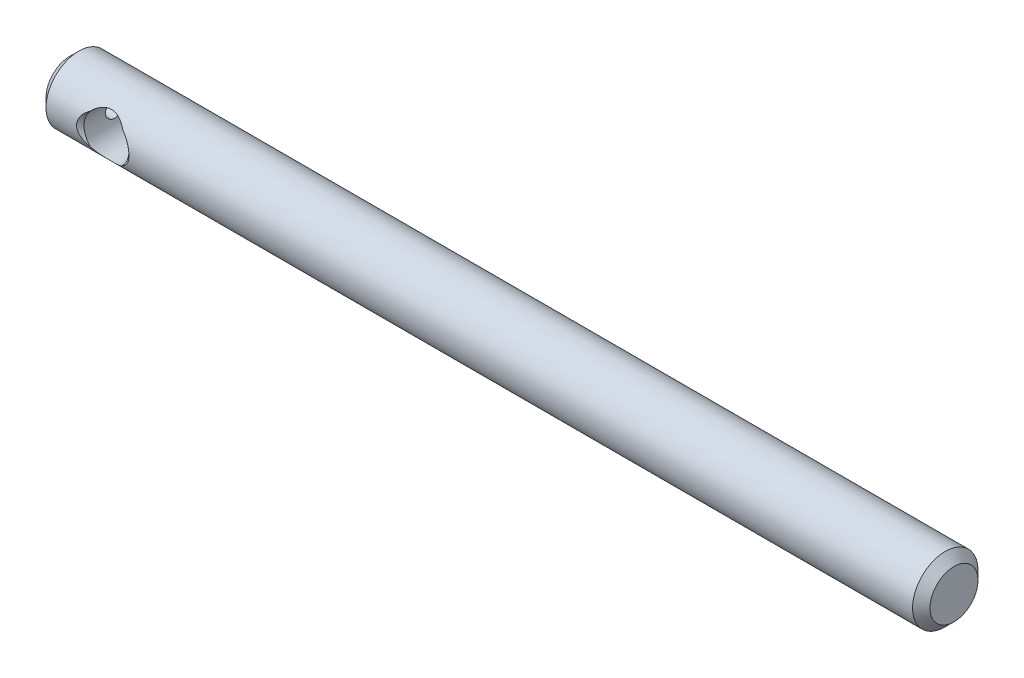
SolidWorks part; units mm, degrees
ref_plane "Front Plane" through (0, 0, 0) normal (0, 0, 1) x (1, 0, 0)
ref_plane "Top Plane" through (0, 0, 0) normal (0, 1, 0) x (1, 0, 0)
ref_plane "Right Plane" through (0, 0, 0) normal (1, 0, 0) x (0, 0, -1)
sketch "Sketch2" plane through (0, 0, 0) normal (1, 0, 0) x (0, 0, -1)
  circle A0 centre (0, 0) radius 4.7625
  dimension "D1" = 9.525
extrude "Boss-Extrude1" add sketch "Sketch2" along normal blind 128.651
chamfer "Chamfer1" distance 1.27 angle 45 2 edges at (0, 0, -4.7625) (128.651, 0, -4.7625)
ref_plane "Plane1" through (0, 0, 4.7625) normal (0, 0, 1) x (1, 0, 0)
sketch "Sketch7" plane through (0, 0, 4.7625) normal (0, 0, 1) x (1, 0, 0)
  line L0 (0, 3.4925) -> (0, -3.4925) construction
  line L1 (127.381, 4.7625) -> (1.27, 4.7625) construction
  point P0 (9.525, 0)
  point P5 (0, 0)
  dimension "D1" = 9.525
  dimension "D2" = 4.7625
hole_wizard "F (0.257) Diameter Hole2" positions "Sketch7" profile "Sketch9" hole size "F" standard "ANSI Inch" end condition through all
sketch "Sketch9" plane through (9.525, 0, 4.7625) normal (1, 0, 0) x (0, -1, 0)
  line L0 (0, 0) -> (0, 9.525)
  line L1 (0, 9.525) -> (3.81, 9.525)
  line L2 (3.2639, 8.9789) -> (3.2639, 0.5461)
  line L3 (3.2639, 0.5461) -> (3.81, 0)
  line L5 (3.81, 0) -> (0, 0)
  line L6 (-3.2639, 0.5461) -> (-3.81, 0) construction
  line L7 (3.81, 9.525) -> (3.2639, 8.9789)
  line L8 (-3.81, 9.525) -> (-3.2639, 8.9789) construction
  line L11 (0, -6.35) -> (0, 107.95) construction
  dimension "Thru Hole Dia." = 6.5278
  dimension "Thru Hole Depth" = 9.525
  dimension "Near C'Sink Dia." = 7.62
  dimension "Near C'Sink Angle" = 90
  dimension "Far C'Sink Dia." = 7.62
  dimension "Far C'Sink Angle" = 90
sketch "Sketch10" plane through (0, 0, 0) normal (-1, 0, 0) x (0, 0, 1)
  point P0 (0, 0)
  point P1 (0, 0)
hole_wizard "#4-40 Tapped Hole1" positions "Sketch10" profile "Sketch11" tap size "#4-40" standard "ANSI Inch" end condition up to next
cosmetic thread "Hole Thread1" parameters "D2"=2.8448
sketch "Sketch11" plane through (0, 0, 0) normal (0, 1, 0) x (0, 0, 1)
  line L0 (0, 0) -> (0, 6.2611)
  line L1 (0, 6.2611) -> (1.1303, 6.2611)
  line L2 (1.1303, 6.2611) -> (1.1303, 0.4572)
  line L3 (1.1303, 0.4572) -> (1.5875, 0)
  line L5 (1.5875, 0) -> (0, 0)
  line L6 (-1.1303, 0.4572) -> (-1.5875, 0) construction
  line L11 (0, -6.35) -> (0, 107.95) construction
  dimension "Thru Tap Drill Dia." = 2.2606
  dimension "Thru Tap Drill Depth" = 6.2611
  dimension "Near C'Sink Dia." = 3.175
  dimension "Near C'Sink Angle" = 90
